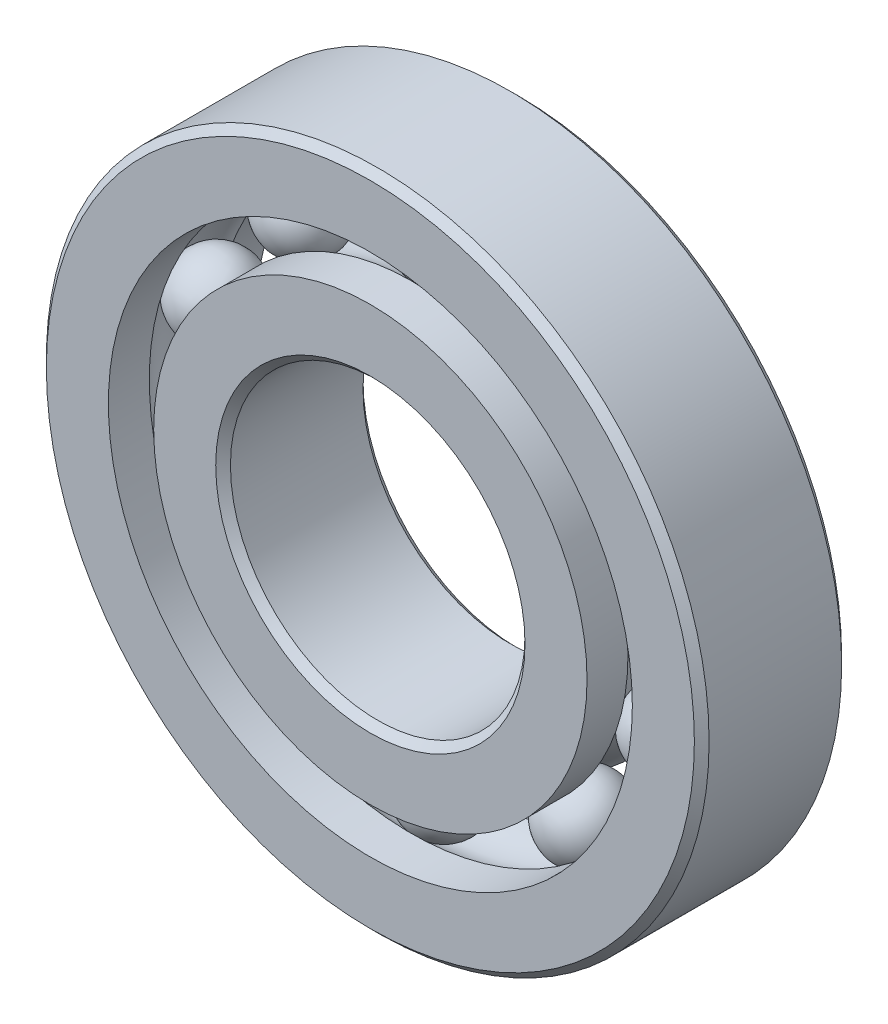
SolidWorks part; units mm, degrees
ref_plane "Front Plane" through (0, 0, 0) normal (0, 0, 1) x (1, 0, 0)
ref_plane "Top Plane" through (0, 0, 0) normal (0, 1, 0) x (1, 0, 0)
ref_plane "Right Plane" through (0, 0, 0) normal (1, 0, 0) x (0, 0, -1)
sketch "Sketch1" plane through (0, 0, 0) normal (1, 0, 0) x (0, 0, -1)
  line L0 (-3.175, 0) -> (3.175, 0) construction
  line L1 (0, 14.2875) -> (0, -14.2875) construction
  line L2 (2.8575, 14.2875) -> (-2.8575, 14.2875)
  line L3 (-2.8575, 14.2875) -> (-3.175, 13.97)
  line L4 (-3.175, 13.97) -> (-3.175, 11.2957)
  line L5 (-3.175, 11.2957) -> (-1.4111, 11.2957)
  line L6 (3.175, 11.2957) -> (1.4111, 11.2957)
  line L7 (3.175, 13.97) -> (3.175, 11.2957)
  line L8 (2.8575, 14.2875) -> (3.175, 13.97)
  line L9 (0, 14.2875) -> (0, 10.3187) construction
  line L10 (0, 10.3187) -> (0, 6.35) construction
  arc A0 (-1.4111, 11.2957) -> (1.4111, 11.2957) centre (0, 10.3187) cw
  point P14 (0, 6.35)
  dimension "Width" = 6.35
  dimension "OD" = 28.575
  dimension "D1" = 45
  dimension "D2" = 0.3175
  dimension "Shaft Dia" = 12.7
  dimension "D3" = 2.8222
  dimension "D4" = 0.9769
revolve "Revolve1" add sketch "Sketch1" angle 360 about L0
sketch "Sketch3" plane through (0, 0, 0) normal (1, 0, 0) x (0, 0, -1)
  line L0 (-3.175, 9.3418) -> (-1.4111, 9.3418)
  line L1 (0, 14.2875) -> (0, -14.2875) construction
  line L2 (-3.175, 13.97) -> (-3.175, 11.2957) construction
  line L3 (-3.175, 9.3418) -> (-3.175, 6.6675)
  line L4 (-2.8575, 14.2875) -> (-3.175, 13.97) construction
  line L5 (-3.175, 6.6675) -> (-2.8575, 6.35)
  line L6 (-2.8575, 6.35) -> (2.8575, 6.35)
  line L7 (2.8575, 14.2875) -> (2.8575, -14.2875) construction
  line L8 (2.8575, 6.35) -> (3.175, 6.6675)
  line L9 (3.175, -13.97) -> (3.175, 13.97) construction
  line L10 (3.175, 6.6675) -> (3.175, 9.3418)
  line L11 (3.175, 9.3418) -> (1.4111, 9.3418)
  line L13 (2.8575, 14.2875) -> (3.175, 13.97) construction
  arc A0 (1.4111, 11.2957) -> (-1.4111, 11.2957) centre (0, 10.3187) ccw construction
  arc A1 (1.4111, 9.3418) -> (-1.4111, 9.3418) centre (0, 10.3187) cw
revolve "Revolve3" add sketch "Sketch3" angle 360 about L0
sketch "Sketch4" plane through (0, 0, 0) normal (1, 0, 0) x (0, 0, -1)
  line L0 (-1.7163, 10.3187) -> (1.7163, 10.3187)
  arc A2 (-1.7163, 10.3187) -> (1.7163, 10.3187) centre (0, 10.3187) cw
  arc A3 (1.4111, 11.2957) -> (-1.4111, 11.2957) centre (0, 10.3187) ccw construction
revolve "Revolve4" add sketch "Sketch4" angle 360 about L0
ref_axis "Axis1" through (0, 0, -3.175) along (0, 0, 1)
pattern_circular "CirPattern1" count 10 every 36 about axis through (0, 0, -3.175) along (0, 0, 1) of bodies 104
sketch "Sketch5" plane through (0, 0, 0) normal (1, 0, 0) x (0, 0, -1)
  line L0 (-3.175, 11.2957) -> (-1.4111, 11.2957) construction
  line L1 (-3.0163, 11.2957) -> (-1.7163, 11.2957)
  line L2 (-3.0163, 11.2957) -> (-3.0163, 9.3418)
  line L3 (-3.0163, 9.3418) -> (-1.7163, 9.3418)
  line L4 (-1.7163, 11.2957) -> (-1.7163, 9.3418)
  line L5 (-3.175, 9.3418) -> (-1.4111, 9.3418) construction
  line L6 (3.175, 11.2957) -> (1.4111, 11.2957) construction
  line L7 (3.0163, 11.2957) -> (1.7163, 11.2957)
  line L8 (3.0163, 11.2957) -> (3.0163, 9.3418)
  line L9 (3.0163, 9.3418) -> (1.7163, 9.3418)
  line L10 (1.7163, 11.2957) -> (1.7163, 9.3418)
  line L11 (3.175, 9.3418) -> (1.4111, 9.3418) construction
  line L12 (-2.8575, 14.2875) -> (-3.175, 13.97) construction
  point P18 (-3.0163, 14.1287)
revolve "Revolve5" [suppressed] add sketch "Sketch5" angle 360 about L0
equation "\"D2@Sketch1\" = \"Width@Sketch1\"*.05"
equation "\"D3@Sketch1\" = \"Width@Sketch1\"/2.25"
equation "\"D4@Sketch1\" = (((\"OD@Sketch1\"-\"Width@Sketch1\")/2)/3.25)/3.5"
equation "\"D2@CirPattern1\" = 360/\"Balls@CirPattern1\""
